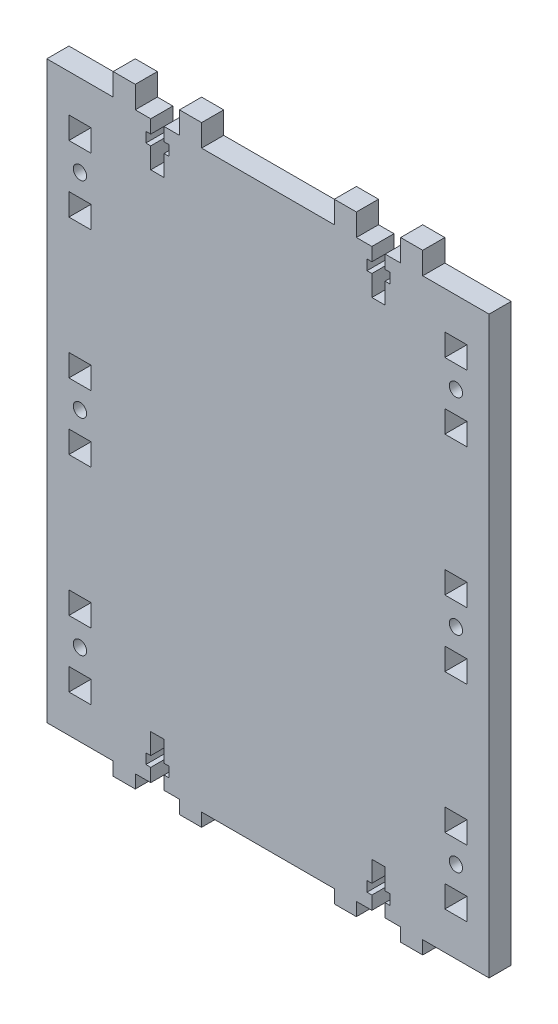
SolidWorks part; units mm, degrees
ref_plane "Front Plane" through (0, 0, 0) normal (0, 0, 1) x (1, 0, 0)
ref_plane "Top Plane" through (0, 0, 0) normal (0, 1, 0) x (1, 0, 0)
ref_plane "Right Plane" through (0, 0, 0) normal (1, 0, 0) x (0, 0, -1)
sketch "Sketch1" plane through (0, 0, 0) normal (0, 0, 1) x (1, 0, 0)
  line L0 (0, 0) -> (0, 38.9816) construction
  line L1 (-40, -65) -> (40, -65) construction
  line L2 (-40, -65) -> (-40, 65) construction
  line L3 (-40, 65) -> (40, 65) construction
  line L4 (40, -65) -> (40, 65) construction
  line L5 (-40, -65) -> (40, 65) construction
  line L6 (-40, 65) -> (40, -65) construction
  line L7 (-50, -65) -> (50, -65)
  line L8 (-50, -65) -> (-50, 65)
  line L9 (-50, 65) -> (50, 65)
  line L10 (50, -65) -> (50, 65)
  line L11 (-50, -65) -> (50, 65) construction
  line L12 (-50, 65) -> (50, -65) construction
  line L13 (0, 0) -> (33.0976, 0) construction
  line L15 (-35, 68) -> (-30, 68)
  line L16 (-35, 68) -> (-35, 70)
  line L17 (-35, 70) -> (-30, 70)
  line L18 (-30, 68) -> (-30, 70)
  line L19 (-20, 68) -> (-15, 68)
  line L20 (-20, 68) -> (-20, 70)
  line L21 (-20, 70) -> (-15, 70)
  line L22 (-15, 68) -> (-15, 70)
  line L23 (15, 68) -> (20, 68)
  line L24 (15, 68) -> (15, 70)
  line L25 (15, 70) -> (20, 70)
  line L26 (20, 68) -> (20, 70)
  line L27 (30, 68) -> (35, 68)
  line L28 (30, 68) -> (30, 70)
  line L29 (30, 70) -> (35, 70)
  line L30 (35, 68) -> (35, 70)
  point P1 (0, 0)
  point P6 (0, 0)
  point P11 (25, 58.3911)
  line B0 (42.5, 41.5) -> (42.5, 51.5) construction
  line B1 (40, 41.5) -> (40, 36.5)
  line B2 (40, 41.5) -> (45, 41.5)
  line B3 (45, 41.5) -> (45, 36.5)
  line B4 (40, 36.5) -> (45, 36.5)
  line B5 (40, 51.5) -> (40, 56.5)
  line B6 (40, 51.5) -> (45, 51.5)
  line B7 (45, 51.5) -> (45, 56.5)
  line B8 (40, 56.5) -> (45, 56.5)
  line B9 (42.5, 46.5) -> (35.5276, 46.5) construction
  circle B10 centre (42.5, 46.5) radius 1.5
  line B11 (42.5, -5) -> (42.5, 5) construction
  line B12 (40, -5) -> (40, -10)
  line B13 (40, -5) -> (45, -5)
  line B14 (45, -5) -> (45, -10)
  line B15 (40, -10) -> (45, -10)
  line B16 (40, 5) -> (40, 10)
  line B17 (40, 5) -> (45, 5)
  line B18 (45, 5) -> (45, 10)
  line B19 (40, 10) -> (45, 10)
  line B20 (42.5, 0) -> (35.5276, 0) construction
  circle B21 centre (42.5, 0) radius 1.5
  line B22 (42.5, -41.5) -> (42.5, -51.5) construction
  line B23 (40, -41.5) -> (40, -36.5)
  line B24 (40, -41.5) -> (45, -41.5)
  line B25 (45, -41.5) -> (45, -36.5)
  line B26 (40, -36.5) -> (45, -36.5)
  line B27 (40, -51.5) -> (40, -56.5)
  line B28 (40, -51.5) -> (45, -51.5)
  line B29 (45, -51.5) -> (45, -56.5)
  line B30 (40, -56.5) -> (45, -56.5)
  line B31 (42.5, -46.5) -> (35.5276, -46.5) construction
  circle B32 centre (42.5, -46.5) radius 1.5
  line B33 (-42.5, -5) -> (-42.5, 5) construction
  line B34 (-40, -5) -> (-40, -10)
  line B35 (-40, -5) -> (-45, -5)
  line B36 (-45, -5) -> (-45, -10)
  line B37 (-40, -10) -> (-45, -10)
  line B38 (-40, 5) -> (-40, 10)
  line B39 (-40, 5) -> (-45, 5)
  line B40 (-45, 5) -> (-45, 10)
  line B41 (-40, 10) -> (-45, 10)
  line B42 (-42.5, 0) -> (-35.5276, 0) construction
  circle B43 centre (-42.5, 0) radius 1.5
  line B44 (-42.5, 41.5) -> (-42.5, 51.5) construction
  line B45 (-40, 41.5) -> (-40, 36.5)
  line B46 (-40, 41.5) -> (-45, 41.5)
  line B47 (-45, 41.5) -> (-45, 36.5)
  line B48 (-40, 36.5) -> (-45, 36.5)
  line B49 (-40, 51.5) -> (-40, 56.5)
  line B50 (-40, 51.5) -> (-45, 51.5)
  line B51 (-45, 51.5) -> (-45, 56.5)
  line B52 (-40, 56.5) -> (-45, 56.5)
  line B53 (-42.5, 46.5) -> (-35.5276, 46.5) construction
  circle B54 centre (-42.5, 46.5) radius 1.5
  line B55 (-42.5, -41.5) -> (-42.5, -51.5) construction
  line B56 (-40, -41.5) -> (-40, -36.5)
  line B57 (-40, -41.5) -> (-45, -41.5)
  line B58 (-45, -41.5) -> (-45, -36.5)
  line B59 (-40, -36.5) -> (-45, -36.5)
  line B60 (-40, -51.5) -> (-40, -56.5)
  line B61 (-40, -51.5) -> (-45, -51.5)
  line B62 (-45, -51.5) -> (-45, -56.5)
  line B63 (-40, -56.5) -> (-45, -56.5)
  line B64 (-42.5, -46.5) -> (-35.5276, -46.5) construction
  circle B65 centre (-42.5, -46.5) radius 1.5
  line B66 (-27.6, -62) -> (-27.6, -59.7)
  line B67 (-23.5, -59.7) -> (-23.5, -55)
  line B68 (-26.5, -55) -> (-26.5, -59.7)
  line B69 (-27.6, -59.7) -> (-26.5, -59.7)
  line B70 (-25, -65) -> (-25, -51.7823) construction
  line B71 (-26.5, -65) -> (-30, -65)
  line B72 (-30, -68) -> (-35, -68)
  line B73 (-35, -68) -> (-35, -65)
  line B74 (-30, -68) -> (-30, -65)
  line B75 (-23.5, -65) -> (-20, -65)
  line B76 (-20, -65) -> (-20, -68)
  line B77 (-20, -68) -> (-15, -68)
  line B78 (-15, -68) -> (-15, -65)
  line B79 (-26.5, -65) -> (-23.5, -65) construction
  line B80 (-23.5, -65) -> (-23.5, -62)
  line B81 (-23.5, -59.7) -> (-22.4, -59.7)
  line B82 (-22.4, -62) -> (-23.5, -62)
  line B83 (-23.5, -55) -> (-26.5, -55)
  line B84 (-26.5, -62) -> (-27.6, -62)
  line B85 (-22.4, -59.7) -> (-22.4, -62)
  line B86 (-26.5, -62) -> (-26.5, -65)
  line B87 (-25, -55) -> (-25, -65) construction
  line B88 (27.6, -62) -> (27.6, -59.7)
  line B89 (23.5, -59.7) -> (23.5, -55)
  line B90 (26.5, -55) -> (26.5, -59.7)
  line B91 (27.6, -59.7) -> (26.5, -59.7)
  line B92 (25, -65) -> (25, -51.7823) construction
  line B93 (26.5, -65) -> (30, -65)
  line B94 (30, -68) -> (35, -68)
  line B95 (35, -68) -> (35, -65)
  line B96 (30, -68) -> (30, -65)
  line B97 (23.5, -65) -> (20, -65)
  line B98 (20, -65) -> (20, -68)
  line B99 (20, -68) -> (15, -68)
  line B100 (15, -68) -> (15, -65)
  line B101 (26.5, -65) -> (23.5, -65) construction
  line B102 (23.5, -65) -> (23.5, -62)
  line B103 (23.5, -59.7) -> (22.4, -59.7)
  line B104 (22.4, -62) -> (23.5, -62)
  line B105 (23.5, -55) -> (26.5, -55)
  line B106 (26.5, -62) -> (27.6, -62)
  line B107 (22.4, -59.7) -> (22.4, -62)
  line B108 (26.5, -62) -> (26.5, -65)
  line B109 (25, -55) -> (25, -65) construction
  line B110 (-22.4, 62) -> (-22.4, 59.7)
  line B111 (-26.5, 59.7) -> (-26.5, 55)
  line B112 (-23.5, 55) -> (-23.5, 59.7)
  line B113 (-22.4, 59.7) -> (-23.5, 59.7)
  line B114 (-25, 65) -> (-25, 51.7823) construction
  line B115 (-23.5, 65) -> (-20, 65)
  line B116 (-20, 68) -> (-15, 68)
  line B117 (-15, 68) -> (-15, 65)
  line B118 (-20, 68) -> (-20, 65)
  line B119 (-26.5, 65) -> (-30, 65)
  line B120 (-30, 65) -> (-30, 68)
  line B121 (-30, 68) -> (-35, 68)
  line B122 (-35, 68) -> (-35, 65)
  line B123 (-23.5, 65) -> (-26.5, 65) construction
  line B124 (-26.5, 65) -> (-26.5, 62)
  line B125 (-26.5, 59.7) -> (-27.6, 59.7)
  line B126 (-27.6, 62) -> (-26.5, 62)
  line B127 (-26.5, 55) -> (-23.5, 55)
  line B128 (-23.5, 62) -> (-22.4, 62)
  line B129 (-27.6, 59.7) -> (-27.6, 62)
  line B130 (-23.5, 62) -> (-23.5, 65)
  line B131 (-25, 55) -> (-25, 65) construction
  line B132 (27.6, 62) -> (27.6, 59.7)
  line B133 (23.5, 59.7) -> (23.5, 55)
  line B134 (26.5, 55) -> (26.5, 59.7)
  line B135 (27.6, 59.7) -> (26.5, 59.7)
  line B136 (25, 65) -> (25, 51.7823) construction
  line B137 (26.5, 65) -> (30, 65)
  line B138 (30, 68) -> (35, 68)
  line B139 (35, 68) -> (35, 65)
  line B140 (30, 68) -> (30, 65)
  line B141 (23.5, 65) -> (20, 65)
  line B142 (20, 65) -> (20, 68)
  line B143 (20, 68) -> (15, 68)
  line B144 (15, 68) -> (15, 65)
  line B145 (26.5, 65) -> (23.5, 65) construction
  line B146 (23.5, 65) -> (23.5, 62)
  line B147 (23.5, 59.7) -> (22.4, 59.7)
  line B148 (22.4, 62) -> (23.5, 62)
  line B149 (23.5, 55) -> (26.5, 55)
  line B150 (26.5, 62) -> (27.6, 62)
  line B151 (22.4, 59.7) -> (22.4, 62)
  line B152 (26.5, 62) -> (26.5, 65)
  line B153 (25, 55) -> (25, 65) construction
  dimension "D1" = 130
  dimension "D2" = 80
  dimension "D3" = 18.5
  dimension "D4" = 25
  dimension "D5" = 100
  dimension "D6" = 2
  dimension "D7" = 5
sketch_block_instance "Trou M3 plots 5mm-1"
sketch_block "Trou M3 plots 5mm" parameters "D2"=3, "D1"=5, "D3"=5, "D4"=10
sketch_block_instance "Trou M3 plots 5mm-2"
sketch_block_instance "Trou M3 plots 5mm-5"
sketch_block_instance "Trou M3 plots 5mm-6"
sketch_block_instance "Trou M3 plots 5mm-7"
sketch_block_instance "Trou M3 plots 5mm-8"
sketch_block_instance "Insert M3 plots ep 3mm-1"
sketch_block "Insert M3 plots ep 3mm" parameters "D1"=10, "D2"=5, "D3"=3
sketch_block_instance "Decoupe Insert M3-4"
sketch_block "Decoupe Insert M3" parameters "D1"=5.2, "D2"=3, "D3"=2.3, "D4"=3, "D5"=10
sketch_block_instance "Insert M3 plots ep 3mm-5"
sketch_block_instance "Insert M3 plots ep 3mm-12"
sketch_block_instance "Insert M3 plots ep 3mm-14"
extrude "Boss-Extrude1" add sketch "Sketch1" along normal blind 5 contours B152 B150 B132 B135 B134 B149 B133 B147 B151 B148 B146 L9 B130 B128 B110 B113 B112 B127 B111 B125 B129 B126 B124 L8 L7 B86 B84 B66 B69 B68 B83 B67 B81 B85 B82 B80 B102 | L15 B122 L9 B120 | L19 B118 L9 B117 | L19 L22 L21 L20 | L15 L18 L17 L16 | L23 B144 L9 B142 | L23 L26 L25 L24 | L27 L30 L29 L28 | L27 B140 L9 B139 | B72 B74 L7 B73 | B77 B78 L7 B76 | B100 B99 B98 L7 | B96 B94 B95 L7 region at (0, 0, 0) region at (-32.5, -66.5, 0) region at (-32.5, 66.5, 0) region at (-32.5, 69, 0) region at (-17.5, -66.5, 0) region at (-17.5, 66.5, 0) region at (17.5, -66.5, 0) region at (-17.5, 69, 0) region at (17.5, 66.5, 0) region at (17.5, 69, 0) region at (32.5, -66.5, 0) region at (32.5, 66.5, 0) region at (32.5, 69, 0)
